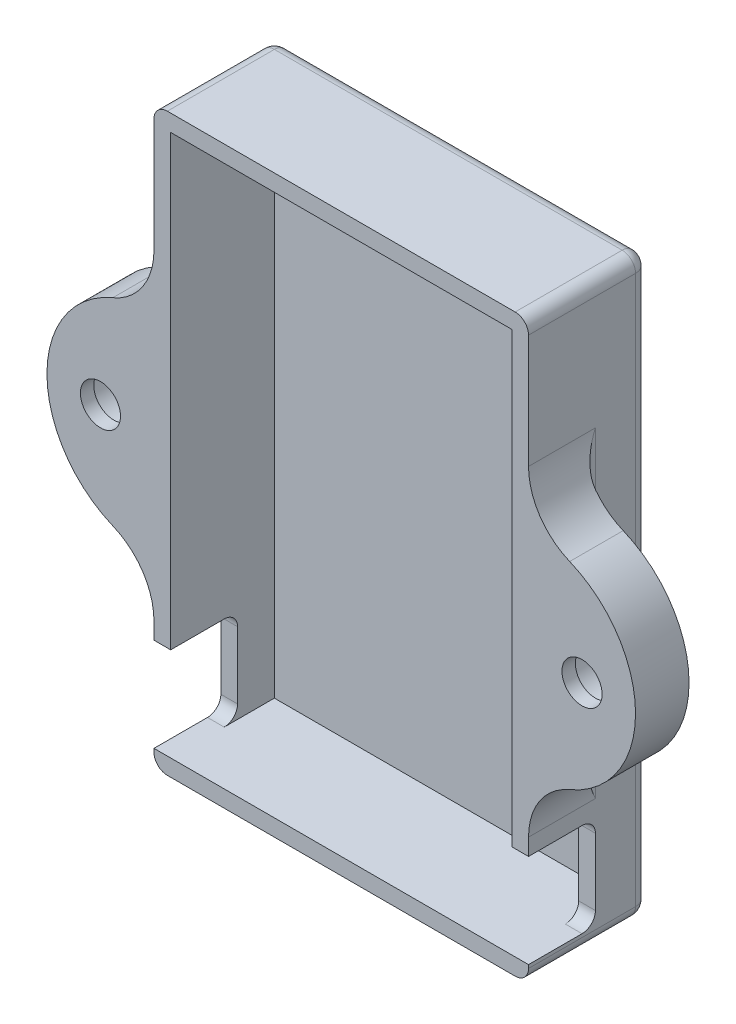
SolidWorks part; units mm, degrees
ref_plane "Front Plane" through (0, 0, 0) normal (0, 0, 1) x (1, 0, 0)
ref_plane "Top Plane" through (0, 0, 0) normal (0, 1, 0) x (1, 0, 0)
ref_plane "Right Plane" through (0, 0, 0) normal (1, 0, 0) x (0, 0, -1)
sketch "Sketch1" plane through (0, 0, 0) normal (0, 0, 1) x (1, 0, 0)
  line L1 (15.1021, 5.5422) -> (43.1021, 5.5422)
  line L2 (15.1021, 5.5422) -> (15.1021, -37.4578)
  line L3 (15.1021, -37.4578) -> (43.1021, -37.4578)
  line L4 (43.1021, 5.5422) -> (43.1021, -37.4578)
  dimension "D1" = 43
  dimension "D2" = 28
extrude "Boss-Extrude1" add sketch "Sketch1" along normal blind 1.25
sketch "Sketch2" plane through (0, 0, 1.25) normal (0, 0, 1) x (1, 0, 0)
  line L0 (43.1021, -37.4578) -> (43.1021, 5.5422) construction
  line L1 (16.3521, 4.2922) -> (41.8521, 4.2922)
  line L2 (16.3521, 4.2922) -> (16.3521, -36.2078)
  line L3 (16.3521, -36.2078) -> (41.8521, -36.2078)
  line L4 (41.8521, 4.2922) -> (41.8521, -36.2078)
  line L5 (43.1021, 5.5422) -> (15.1021, 5.5422) construction
  line L6 (15.1021, 5.5422) -> (15.1021, -37.4578) construction
  line L7 (15.1021, -37.4578) -> (43.1021, -37.4578) construction
  line L8 (15.1021, 5.5422) -> (15.1021, -37.4578)
  line L9 (15.1021, 5.5422) -> (43.1021, 5.5422)
  line L12 (43.1021, 5.5422) -> (43.1021, -37.4578)
  line L13 (15.1021, -37.4578) -> (43.1021, -37.4578)
  dimension "D1" = 1.25
  dimension "D2" = 1.25
  dimension "D3" = 1.25
  dimension "D4" = 1.25
extrude "Boss-Extrude2" add sketch "Sketch2" along normal blind 2.75
sketch "Sketch4" plane through (0, 0, 4) normal (0, 0, 1) x (1, 0, 0)
  line L0 (29.1021, 4.2922) -> (29.1021, -7.3909) construction
  line L1 (43.1021, -36.2078) -> (15.1021, -36.2078)
  line L2 (41.8521, -29.2078) -> (41.8521, 4.2922)
  line L3 (41.8521, -36.2078) -> (41.8521, 4.2922) construction
  line L4 (41.8521, 4.2922) -> (16.3521, 4.2922) construction
  line L5 (41.8521, 4.2922) -> (16.3521, 4.2922)
  line L8 (15.1021, -37.4578) -> (43.1021, -37.4578)
  line L9 (43.1021, -37.4578) -> (43.1021, 5.5422) construction
  line L10 (15.1021, -29.2078) -> (15.1021, 5.5422)
  line L11 (16.3521, -36.2078) -> (41.8521, -36.2078) construction
  line L12 (43.1021, -37.4578) -> (43.1021, -36.2078)
  line L13 (41.8521, -29.2078) -> (43.1021, -29.2078)
  line L14 (43.1021, -29.2078) -> (43.1021, 5.5422)
  line L15 (43.1021, 5.5422) -> (15.1021, 5.5422) construction
  line L16 (43.1021, 5.5422) -> (15.1021, 5.5422)
  line L17 (16.3521, -29.2078) -> (15.1021, -29.2078)
  line L18 (15.1021, -37.4578) -> (15.1021, -36.2078)
  line L19 (16.3521, -29.2078) -> (16.3521, 4.2922)
  point P9 (29.1021, 4.2922)
  point P27 (29.1021, 5.5422)
  point P32 (29.1021, 4.2922)
  dimension "D1" = 7
extrude "Boss-Extrude3" add sketch "Sketch4" along normal blind 5
sketch "Sketch7" plane through (0, 0, 0) normal (0, 0, -1) x (-1, 0, 0)
  line L0 (-43.1021, 5.5422) -> (-15.1021, 5.5422) construction
  line L1 (-41.8521, 4.2922) -> (-16.3521, 4.2922)
  line L2 (-41.8521, 4.2922) -> (-41.8521, -36.2078)
  line L3 (-41.8521, -36.2078) -> (-16.3521, -36.2078)
  line L4 (-16.3521, 4.2922) -> (-16.3521, -36.2078)
  line L5 (-43.1021, -37.4578) -> (-43.1021, 5.5422) construction
  line L6 (-15.1021, -37.4578) -> (-43.1021, -37.4578) construction
  line L7 (-15.1021, 5.5422) -> (-15.1021, -37.4578) construction
  dimension "D1" = 1.25
  dimension "D2" = 1.25
  dimension "D3" = 1.25
  dimension "D4" = 1.25
sketch "Sketch9" plane through (0, 0, 9) normal (0, 0, 1) x (1, 0, 0)
  line L0 (29.1021, 4.2922) -> (29.1021, -3.6852) construction
  line L1 (15.1021, 5.5422) -> (15.1021, -29.2078) construction
  line L2 (43.1021, 5.5422) -> (15.1021, 5.5422) construction
  line L3 (15.1021, -15.9578) -> (11.1021, -15.9578) construction
  line L4 (15.1021, -7.9578) -> (15.1021, -23.9578)
  line L5 (41.8521, 4.2922) -> (16.3521, 4.2922) construction
  line L6 (43.1021, -15.9578) -> (47.1021, -15.9578) construction
  line L7 (43.1021, -7.9578) -> (43.1021, -23.9578)
  arc A0 (15.1021, -7.9578) -> (15.1021, -23.9578) centre (15.1021, -15.9578) ccw
  circle A1 centre (11.1021, -15.9578) radius 1.5
  circle A2 centre (47.1021, -15.9578) radius 1.5
  arc A3 (43.1021, -7.9578) -> (43.1021, -23.9578) centre (43.1021, -15.9578) cw
  dimension "D3" = 3
  dimension "D1" = 8
  dimension "D2" = 21.5
  dimension "D4" = 4
extrude "Boss-Extrude4" add sketch "Sketch9" against normal blind 4
fillet "Fillet1" radius 1 14 edges at (43.1021, -15.9578, 0) (43.1021, -37.4578, 4.5) (29.1021, -37.4578, 0) (15.1021, -37.4578, 4.5) (15.1021, -15.9578, 0) (29.1021, 5.5422, 0) (15.1021, 5.5422, 4.5) (43.1021, 5.5422, 4.5) (15.1021, -15.9578, 5) (15.7271, -29.2078, 4) (15.7271, -36.2078, 4) (42.4771, -36.2078, 4) (42.4771, -29.2078, 4) (43.1021, -15.9578, 5)
fillet "Fillet2" radius 5 4 edges at (15.1021, -23.9578, 6.5) (15.1021, -7.9578, 6.5) (43.1021, -7.9578, 6.5) (43.1021, -23.9578, 6.5)
sketch "Sketch10" plane through (0, 0, 5) normal (0, 0, -1) x (-1, 0, 0)
  circle A0 centre (-47.1021, -15.9578) radius 2.25
  circle A1 centre (-11.1021, -15.9578) radius 2.25
  dimension "D1" = 4.5
  dimension "D2" = 4.5
extrude "Cut-Extrude1" cut sketch "Sketch10" against normal blind 3
